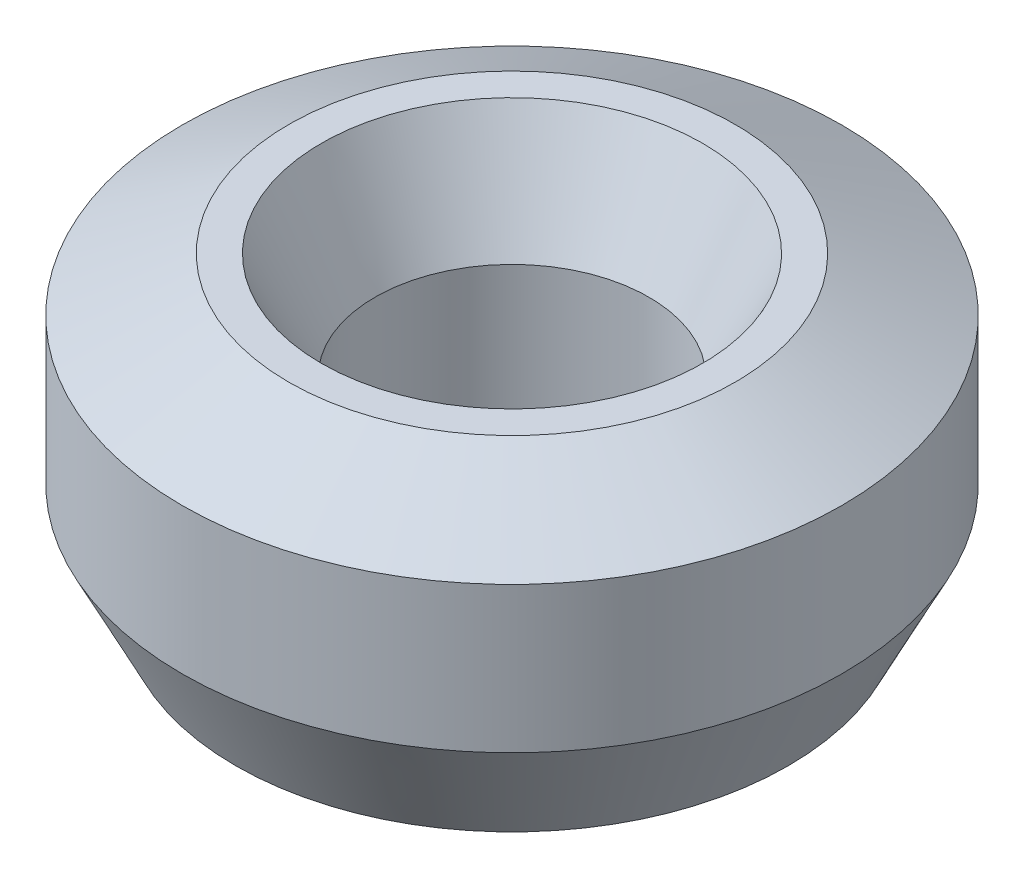
SolidWorks part; units mm, degrees
ref_plane "Front Plane" through (0, 0, 0) normal (0, 0, 1) x (1, 0, 0)
ref_plane "Top Plane" through (0, 0, 0) normal (0, 1, 0) x (1, 0, 0)
ref_plane "Right Plane" through (0, 0, 0) normal (1, 0, 0) x (0, 0, -1)
sketch "Sketch1" plane through (0, 0, 0) normal (0, 1, 0) x (1, 0, 0)
  circle A0 centre (0, 0) radius 17.5
  dimension "SLEEVE_OD" = 35
extrude "Boss-Extrude1" add sketch "Sketch1" along normal blind 16.2373
sketch "Sketch2" plane through (0, 0, 0) normal (0, 1, 0) x (1, 0, 0)
  circle A0 centre (0, 0) radius 7.2722
  dimension "BORE_D" = 14.5443
extrude "Cut-Extrude1" cut sketch "Sketch2" along normal through all
chamfer "Chamfer1" distance 2.8466 angle 63.263 4 edges at (0, 16.2373, 7.2722) (0, 0, 7.2722) (0, 0, 17.5) (0, 16.2373, 17.5) first distance on face at (0, 16.2373, 7.2722) first distance on face at (0, 0, 7.2722) first distance on face at (0, 16.2373, 17.5)
